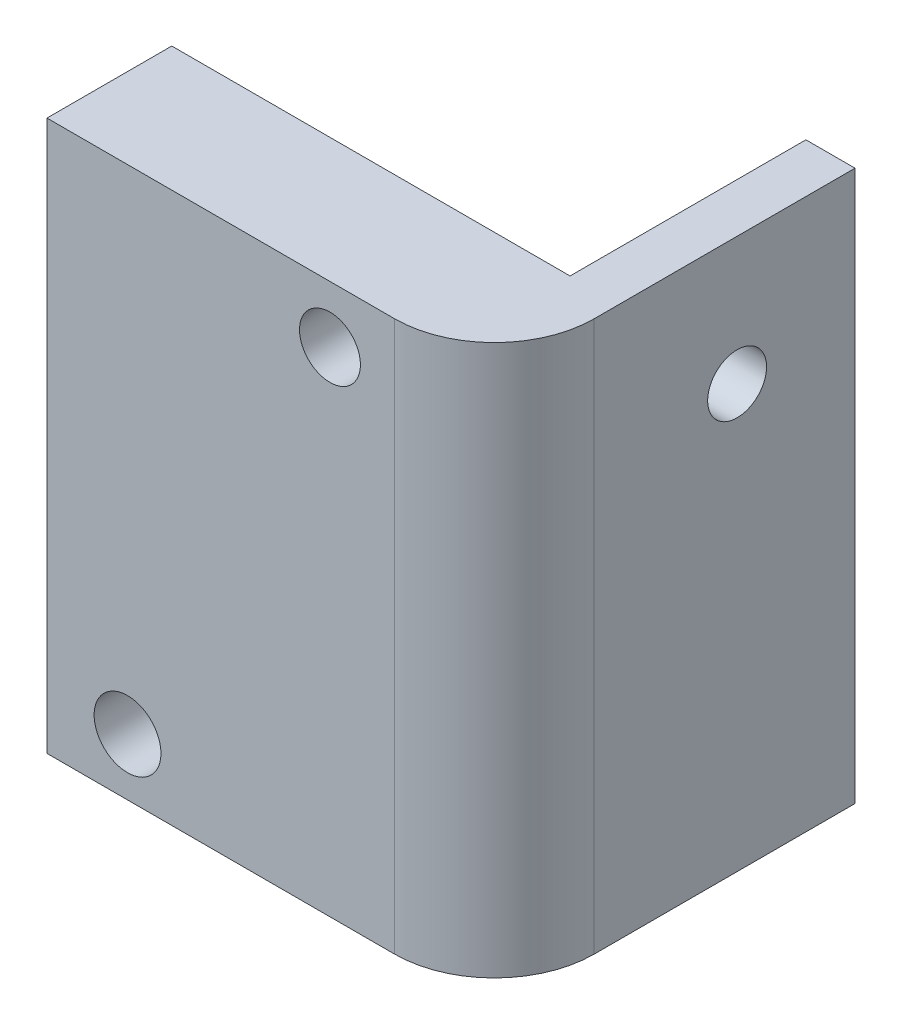
SolidWorks part; units mm, degrees
ref_plane "Front Plane" through (0, 0, 0) normal (0, 0, 1) x (1, 0, 0)
ref_plane "Top Plane" through (0, 0, 0) normal (0, 1, 0) x (1, 0, 0)
ref_plane "Right Plane" through (0, 0, 0) normal (1, 0, 0) x (0, 0, -1)
sketch "Sketch1" plane through (0, 0, 0) normal (0, 1, 0) x (1, 0, 0)
  line L0 (0, 18.35) -> (0, 0)
  line L1 (0, 0) -> (-22.7672, 0)
  line L2 (-22.7672, 0) -> (-22.7672, 6.35)
  line L3 (-22.7672, 6.35) -> (-2.5, 6.35)
  line L4 (-2.5, 6.35) -> (-2.5, 18.35)
  line L5 (-2.5, 18.35) -> (0, 18.35)
  dimension "D1" = 6.35
  dimension "D2" = 2.5
  dimension "D3" = 20.2672
  dimension "D4" = 12
extrude "Boss-Extrude1" add sketch "Sketch1" along normal blind 28
sketch "Sketch2" plane through (-2.5, 0, 0) normal (-1, 0, 0) x (0, 0, 1)
  line L0 (-12.35, 21.5) -> (-12.35, 6.5) construction
  line L1 (-18.35, 28) -> (-18.35, 0) construction
  line L2 (-18.35, 28) -> (-6.35, 28) construction
  circle A0 centre (-12.35, 21.5) radius 1.5
  circle A1 centre (-12.35, 6.5) radius 1.5
  point P4 (-12.35, 14)
  point P7 (-18.35, 14)
  point P11 (-12.35, 28)
  dimension "D1" = 3
  dimension "D2" = 15
extrude "Cut-Extrude1" cut sketch "Sketch2" against normal through all contours A0 region at (-2.5, 21.5, -12.35)
sketch "Sketch3" plane through (0, 0, 0) normal (0, 0, 1) x (1, 0, 0)
  line L0 (-6.818, 28) -> (-6.818, 0) construction
  line L1 (-22.7672, 28) -> (0, 28) construction
  line L2 (-8.368, 25.1) -> (-8.368, 2.9) construction
  line L3 (-8.368, 2.9) -> (-18.668, 2.9) construction
  line L4 (-18.668, 2.9) -> (-18.668, 25.1) construction
  line L5 (-18.668, 25.1) -> (-8.368, 25.1) construction
  line L6 (0, 28) -> (0, 0) construction
  line L8 (-22.7672, 0) -> (0, 0) construction
  line L9 (-2.5, 28) -> (-2.5, 0) construction
  circle A0 centre (-8.368, 25.1) radius 1.55
  circle A1 centre (-18.668, 2.9) radius 1.7
  point P6 (-8.368, 14)
  point P13 (0, 14)
  dimension "D1" = 3.1
  dimension "D2" = 3.4
  dimension "D5" = 4.318
  dimension "D3" = 22.2
  dimension "D4" = 10.3
extrude "Cut-Extrude2" cut sketch "Sketch3" against normal through all
fillet "Fillet1" radius 5.08 1 edges at (0, 14, 0)
extrude "Boss-Extrude2" add sketch "Sketch2<3>" along normal blind 3.048 contours A1 region at (-2.5, 6.5, -12.35)
sketch "Sketch2<3>" plane through (-2.5, 0, 0) normal (-1, 0, 0) x (0, 0, 1) same geometry as "Sketch2"
